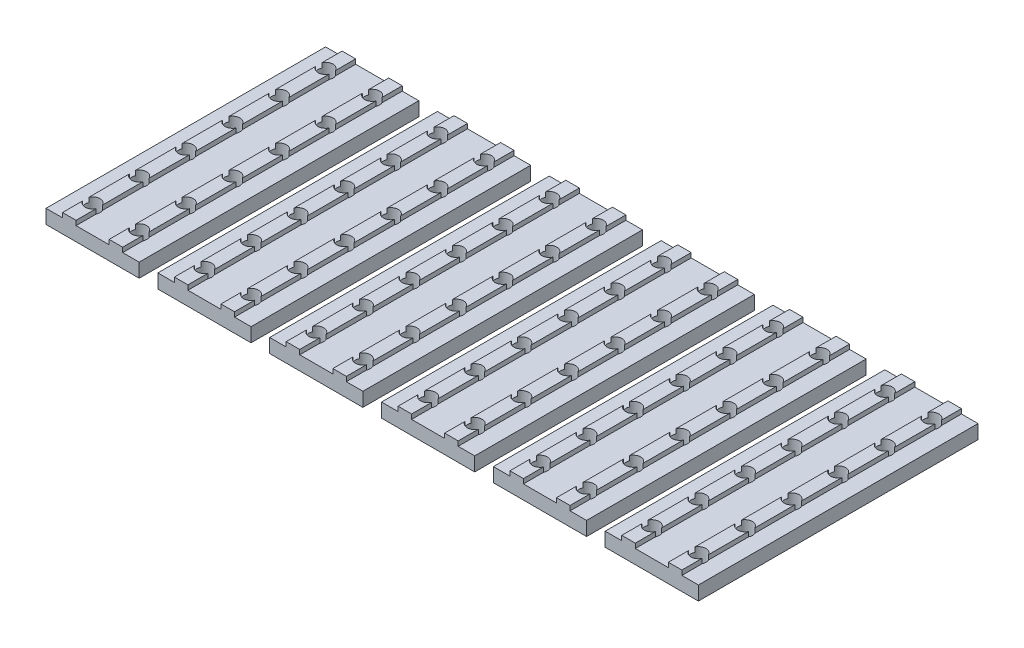
SolidWorks part; units mm, degrees
ref_plane "Front Plane" through (0, 0, 0) normal (0, 0, 1) x (1, 0, 0)
ref_plane "Top Plane" through (0, 0, 0) normal (0, 1, 0) x (1, 0, 0)
ref_plane "Right Plane" through (0, 0, 0) normal (1, 0, 0) x (0, 0, -1)
sketch "Esquisse1" plane through (0, 0, 0) normal (0, 0, 1) x (1, 0, 0)
  line L0 (-5, 0) -> (-5, 3)
  line L1 (-5, 3) -> (-1.45, 3)
  line L2 (-1.45, 3) -> (-1.45, 4)
  line L3 (-1.45, 4) -> (1.45, 4)
  line L4 (1.45, 4) -> (1.45, 3)
  line L5 (1.45, 3) -> (5, 3)
  line L6 (5, 3) -> (5, 0)
  line L7 (5, 0) -> (-5, 0)
  point P11 (0, 0)
  dimension "D1" = 10
  dimension "D2" = 3
  dimension "D3" = 1
  dimension "D4" = 2.9
  dimension "D5" = 3.55
extrude "Main" add sketch "Esquisse1" along normal blind 20
sketch "Esquisse2" plane through (0, 4, 0) normal (0, 1, 0) x (1, 0, 0)
  line L0 (0, -2.2) -> (0, 2.2) construction
  line L1 (-1.45, 0) -> (-5, 0) construction
  line L2 (-1.45, -20) -> (-5, -20) construction
  circle A0 centre (0, -5) radius 1.6
  circle A1 centre (0, -15) radius 1.6
  dimension "D2" = 5
  dimension "D3" = 3.2
  dimension "D1" = 5
extrude "TopHole" cut sketch "Esquisse2" against normal through all
ref_axis "Axe1" through (-5.5, 0, 0) along (1, 0, 0)
pattern_linear "Répétition linéaire1" count 3 spacing 20 along (0, 0, 1) count 2 spacing 10 along (-1, 0, 0) of "TopHole", "Main"
pattern_linear "LPattern1" count 6 spacing 24 along (1, 0, 0) of bodies 103
